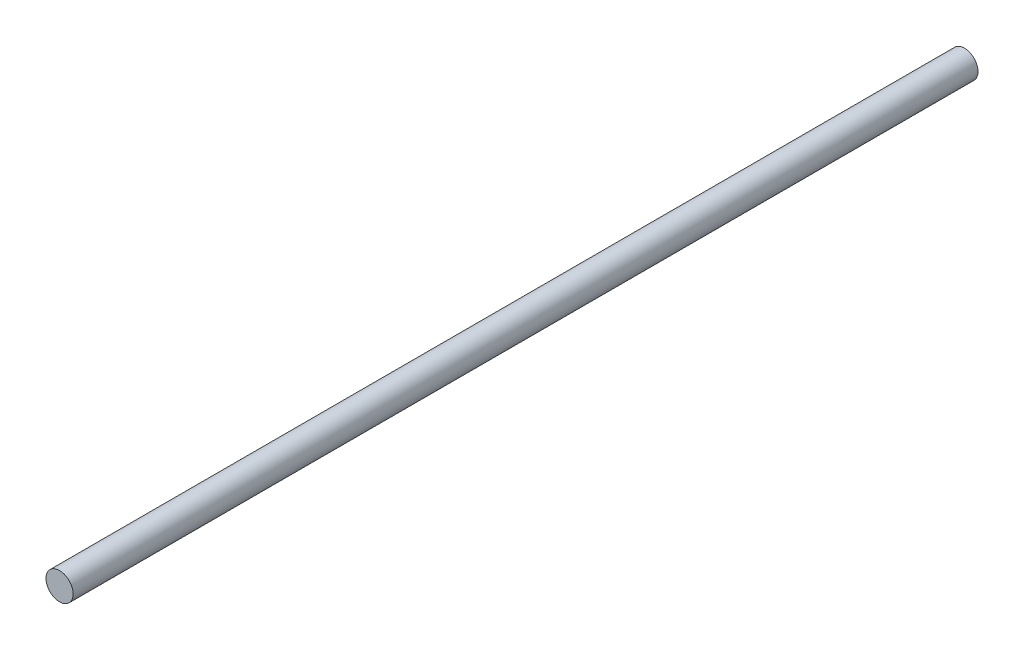
SolidWorks part; units mm, degrees
material "Plain Carbon Steel"
ref_plane "Спереди" through (0, 0, 0) normal (0, 0, 1) x (1, 0, 0)
ref_plane "Сверху" through (0, 0, 0) normal (0, 1, 0) x (1, 0, 0)
ref_plane "Справа" through (0, 0, 0) normal (1, 0, 0) x (0, 0, -1)
sketch "Sketch1" plane through (0, 0, 0) normal (0, 0, 1) x (1, 0, 0)
  circle A0 centre (0, 0) radius 3
  dimension "D1" = 6
extrude "Boss-Extrude1" add sketch "Sketch1" along normal blind 200
